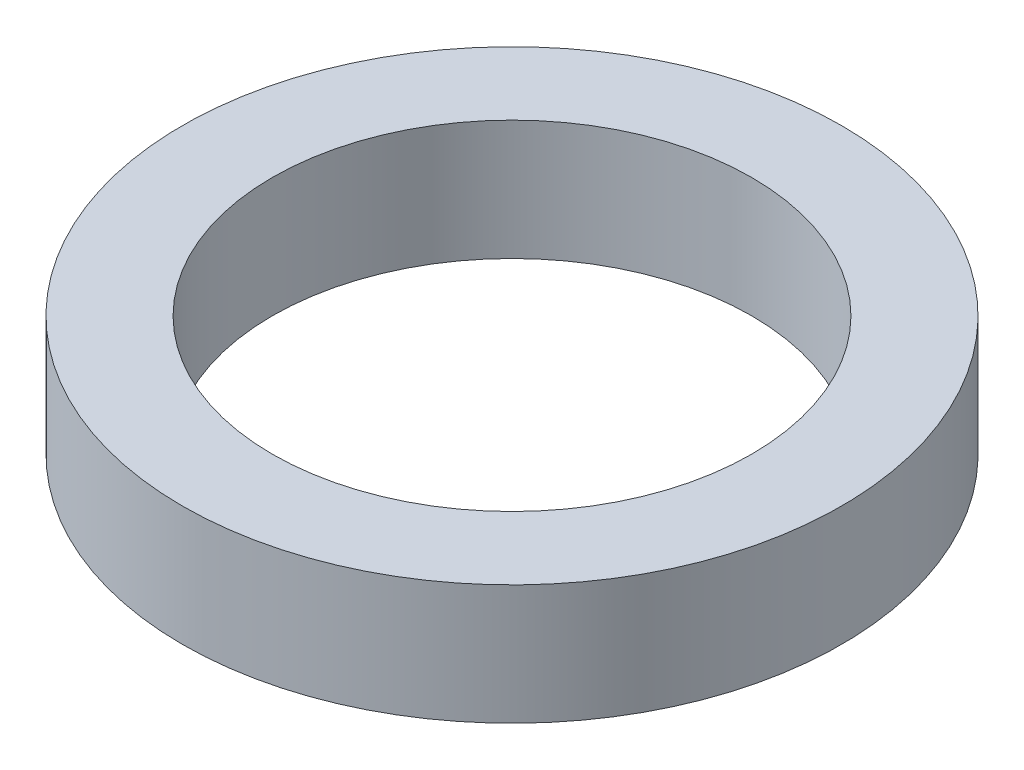
SolidWorks part; units mm, degrees
ref_plane "Front Plane" through (0, 0, 0) normal (0, 0, 1) x (1, 0, 0)
ref_plane "Top Plane" through (0, 0, 0) normal (0, 1, 0) x (1, 0, 0)
ref_plane "Right Plane" through (0, 0, 0) normal (1, 0, 0) x (0, 0, -1)
sketch "Sketch1" plane through (0, 0, 0) normal (0, 1, 0) x (1, 0, 0)
  circle A0 centre (0, 0) radius 27.5
  dimension "FLANGE_OD" = 55
extrude "Boss-Extrude1" add sketch "Sketch1" along normal blind 10
sketch "Sketch2" plane through (0, 0, 0) normal (0, 1, 0) x (1, 0, 0)
  circle A0 centre (0, 0) radius 20
  dimension "BORE_D" = 40
extrude "Cut-Extrude1" cut sketch "Sketch2" along normal through all
sketch "Sketch3" plane through (0, 10, 0) normal (0, 1, 0) x (1, 0, 0)
  circle A0 centre (0, 0) radius 12.1602 construction
  circle A1 centre (-12.1602, 0) radius 1.5
  dimension "BOLT_D" = 3
  dimension "BOLT_PCD" = 24.3204
extrude "Cut-Extrude2" cut sketch "Sketch3" against normal blind 6.9836 rebuild error yes
pattern_circular "CirPattern1" count 5 over 360 rebuild error yes
